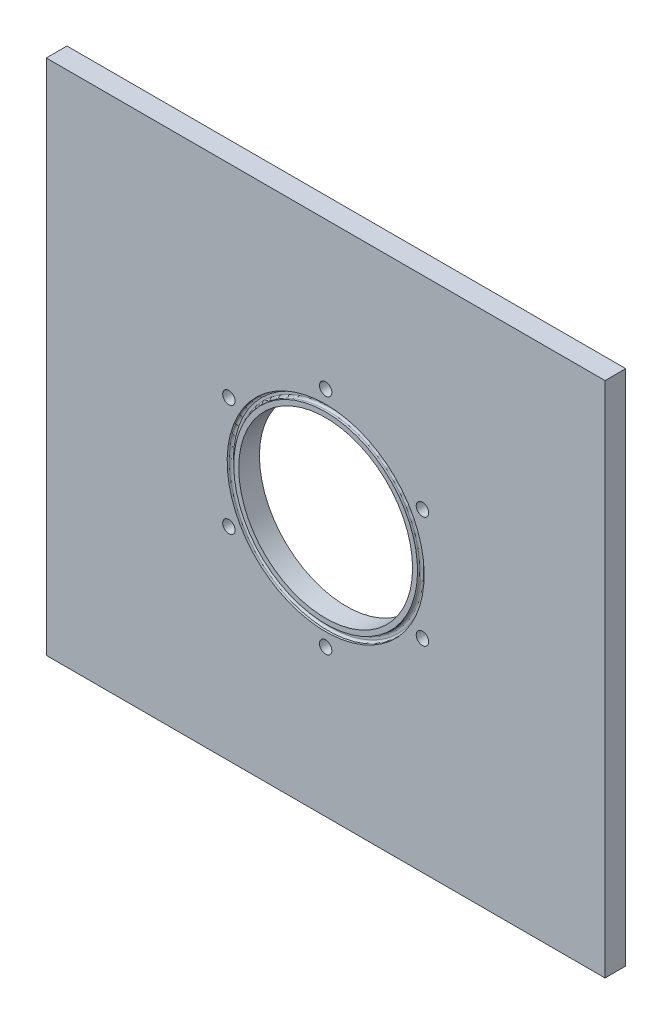
SolidWorks part; units mm, degrees
material "1023 Carbon Steel Sheet (SS)"
ref_plane "Front Plane" through (0, 0, 0) normal (0, 0, 1) x (1, 0, 0)
ref_plane "Top Plane" through (0, 0, 0) normal (0, 1, 0) x (1, 0, 0)
ref_plane "Right Plane" through (0, 0, 0) normal (1, 0, 0) x (0, 0, -1)
sketch "Sketch1" plane through (0, 0, 0) normal (0, 0, 1) x (1, 0, 0)
  line L1 (-67.5, -62.5) -> (67.5, -62.5)
  line L2 (-67.5, -62.5) -> (-67.5, 62.5)
  line L3 (-67.5, 62.5) -> (67.5, 62.5)
  line L4 (67.5, -62.5) -> (67.5, 62.5)
  line L5 (-67.5, -62.5) -> (67.5, 62.5) construction
  line L6 (-67.5, 62.5) -> (67.5, -62.5) construction
  circle A0 centre (0, 0) radius 21
  circle A1 centre (0, 0) radius 27 construction
  circle A2 centre (0, 27) radius 1.5
  circle A3 centre (23.3827, 13.5) radius 1.5
  circle A4 centre (23.3827, -13.5) radius 1.5
  circle A5 centre (0, -27) radius 1.5
  circle A6 centre (-23.3827, -13.5) radius 1.5
  circle A7 centre (-23.3827, 13.5) radius 1.5
  point P0 (0, 0)
  point P23 (0, 0)
  dimension "D3" = 42
  dimension "D4" = 54
  dimension "D5" = 3
  dimension "D1" = 135
  dimension "D2" = 125
  dimension "D6" = 6
extrude "Boss-Extrude1" add sketch "Sketch1" along normal blind 5 contours L1 L4 L3 L2 A7 A6 A5 A4 A3 A2 A0 | A5 | A6 | A4 | A3 | A2 | A7 region at (-65.6602, 0, 0) region at (0, -27, 0)
extrude "Cut-Extrude1" cut sketch "Sketch1<3>" against normal blind 3 from surface contours A6 | A7 | A2 | A3 | A4 | A5 starting at face at (21, 0, 5)
sketch "Sketch1<3>" plane through (0, 0, 0) normal (0, 0, 1) x (1, 0, 0) same geometry as "Sketch1"
sketch "Sketch2" plane through (0, 0, 0) normal (0, 0, -1) x (-1, 0, 0)
  circle A0 centre (27, 0) radius 1.5
  circle A1 centre (-27, 0) radius 1.5
  circle A2 centre (0, 0) radius 27 construction
  dimension "D1" = 54
  dimension "D2" = 3
extrude "Cut-Extrude2" cut sketch "Sketch2" against normal blind 3
sketch "Sketch3" plane through (0, 0, 0) normal (1, 0, 0) x (0, 0, -1)
  line L0 (-5, 23.8) -> (-4.5, 23.8)
  line L1 (-5, -62.5) -> (-5, 62.5) construction
  line L2 (-4, 23.3) -> (-4, 22.7)
  line L3 (-4.5, 22.2) -> (-5, 22.2)
  line L4 (-5, 22.2) -> (-5, 23.8)
  line L5 (0, 0) -> (-22.1802, 0) construction
  arc A0 (-4, 22.7) -> (-4.5, 22.2) centre (-4.5, 22.7) cw
  arc A1 (-4.5, 23.8) -> (-4, 23.3) centre (-4.5, 23.3) cw
  point P7 (-4, 23)
  point P10 (-4, 22.2)
  point P15 (-4, 23.8)
  dimension "D4" = 0.5
  dimension "D1" = 23
  dimension "D2" = 1.6
  dimension "D3" = 1
revolve "Cut-Revolve1" cut sketch "Sketch3" angle 360 about L5
